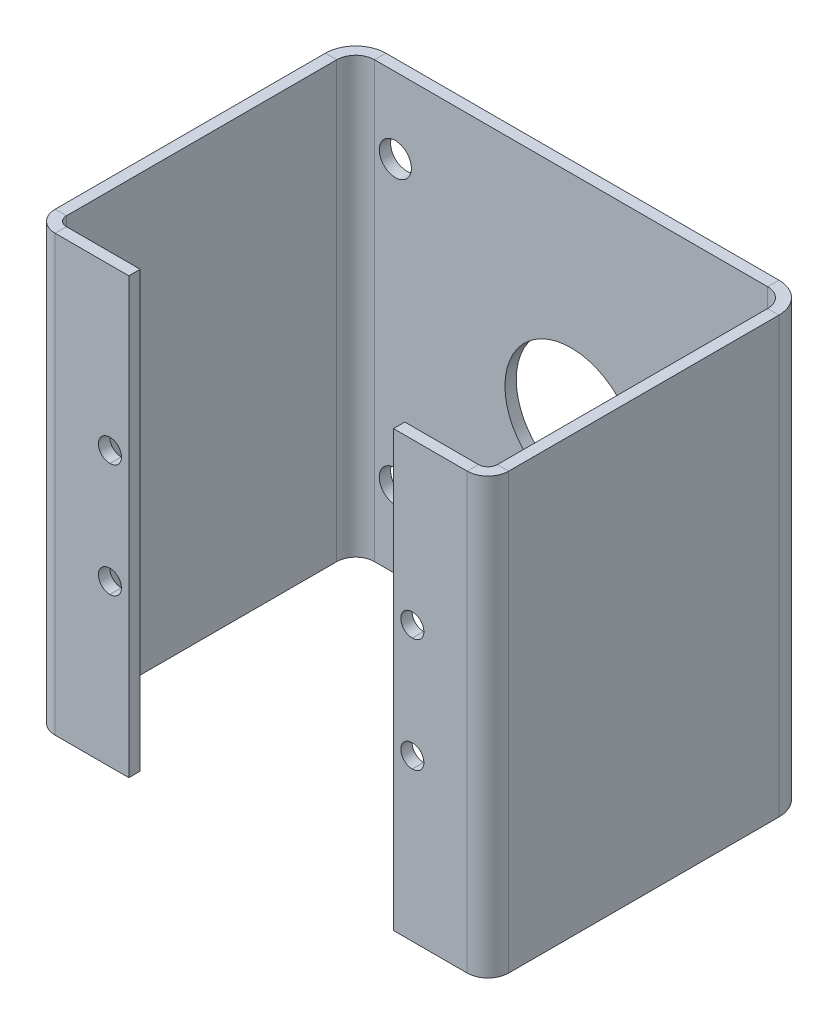
SolidWorks part; units mm, degrees
note: The reader was unsure of these and kept them because the rebuilt part matched: thickness of "Base-Flange1", "Edge-Flange1", "Edge-Flange2", "Sheet-Metal1", "Sheet-Metal2", "Sheet-Metal3", "Sheet-Metal4", "Sheet-Metal5", "Sheet-Metal7", "Sheet-Metal8", "Sheet-Metal9", "Sheet-Metal10"; flange length of "Edge-Flange1", "Edge-Flange2".
material "ASTM A36 Steel"
ref_plane "Front Plane" through (0, 0, 0) normal (0, 0, 1) x (1, 0, 0)
ref_plane "Top Plane" through (0, 0, 0) normal (0, 1, 0) x (1, 0, 0)
ref_plane "Right Plane" through (0, 0, 0) normal (1, 0, 0) x (0, 0, -1)
sketch "Sketch1" plane through (0, 0, 0) normal (0, 0, 1) x (1, 0, 0)
  line L1 (-60, -57.5) -> (60, -57.5)
  line L2 (-60, -57.5) -> (-60, 57.5)
  line L3 (-60, 57.5) -> (60, 57.5)
  line L4 (60, -57.5) -> (60, 57.5)
  line L5 (-60, -57.5) -> (60, 57.5) construction
  line L6 (-60, 57.5) -> (60, -57.5) construction
  point P0 (0, 0)
  dimension "D1" = 115
  dimension "D2" = 120
base flange "Base-Flange1" sketch "Sketch1" thickness 3 reverse thickness direction no parameters "D1"=2.5
edge flange "Edge-Flange1" sketch "Sketch10" flange profiles "Sketch10", "Sketch11" flange angle 90 flange length 85 flange position material inside bend radius 5 thickness 3 relief rectangular parameters "D6"=10, "D8"=1
sketch "Sketch10" plane through (60, 0, 0) normal (1, 0, 0) x (0, 1, 0)
  line L0 (-57.5, 0) -> (57.5, 0) construction
  line L1 (-57.5, 0) -> (57.5, 0)
  line L2 (-57.5, 0) -> (-57.5, 82)
  line L3 (-57.5, 82) -> (57.5, 82)
  line L4 (57.5, 82) -> (57.5, 0)
sketch "Sketch11" plane through (-60, 0, 0) normal (-1, 0, 0) x (0, -1, 0)
  line L0 (-57.5, 0) -> (57.5, 0) construction
  line L1 (-57.5, 0) -> (57.5, 0)
  line L2 (-57.5, 0) -> (-57.5, 82)
  line L3 (-57.5, 82) -> (57.5, 82)
  line L4 (57.5, 82) -> (57.5, 0)
bend "EdgeBend1" bend radius 5 bend angle 90 parameters "D5"=1
bend "EdgeBend2" bend radius 5 bend angle 90 parameters "D5"=2
edge flange "Edge-Flange2" sketch "Sketch16" flange profiles "Sketch16", "Sketch17" flange angle 90 flange length 25 flange position material inside bend radius 2.5 thickness 3 relief rectangular parameters "D6"=10, "D8"=1
sketch "Sketch16" plane through (-57, 0, 82) normal (0, 0, 1) x (0, -1, 0)
  line L2 (-57.5, 0) -> (-57.5, 22)
  line L3 (-57.5, 22) -> (57.5, 22)
  line L4 (57.5, 22) -> (57.5, 0)
  line L5 (57.5, 0) -> (-57.5, 0) construction
  line L6 (57.5, 0) -> (-57.5, 0)
sketch "Sketch17" plane through (57, 0, 82) normal (0, 0, 1) x (0, 1, 0)
  line L2 (-57.5, 0) -> (-57.5, 22)
  line L3 (-57.5, 22) -> (57.5, 22)
  line L4 (57.5, 22) -> (57.5, 0)
  line L5 (57.5, 0) -> (-57.5, 0) construction
  line L6 (57.5, 0) -> (-57.5, 0)
bend "EdgeBend3" bend radius 2.5 bend angle 90 parameters "D5"=3
bend "EdgeBend4" bend radius 2.5 bend angle 90 parameters "D5"=4
sketch "Sketch18" plane through (0, 0, 82) normal (0, 0, 1) x (1, 0, 0)
  line L0 (-40.05, -15) -> (-39.95, -15) construction
  line L1 (-40.05, -12) -> (-39.95, -12)
  line L2 (-40.05, -18) -> (-39.95, -18)
  line L4 (-54.5, -57.5) -> (-35, -57.5) construction
  line L5 (-60, -57.5) -> (-60, 57.5) construction
  arc A0 (-40.05, -12) -> (-40.05, -18) centre (-40.05, -15) ccw
  arc A1 (-39.95, -18) -> (-39.95, -12) centre (-39.95, -15) ccw
  point P2 (-40, -15)
  point P11 (-44.75, -57.5)
  dimension "D1" = 3
  dimension "D2" = 0.1
  dimension "D3" = 20
  dimension "D4" = 42.5
extrude "Cut-Extrude1" cut sketch "Sketch18" against normal blind 10 normal cut yes
pattern_linear "LPattern1" count 2 spacing 30 along (0, 1, 0) of "Cut-Extrude1"
pattern_linear "LPattern2" count 2 spacing 80 along (1, 0, 0) of "LPattern1", "Cut-Extrude1"
sketch "Sketch19" plane through (0, 0, -3) normal (0, 0, -1) x (-1, 0, 0)
  line L0 (-60, 57.5) -> (-60, -57.5) construction
  line L2 (52, -57.5) -> (-52, -57.5) construction
  circle A0 centre (-46.5, -37.5) radius 4.25
  circle A1 centre (46.5, -37.5) radius 4.25
  dimension "D1" = 13.5
  dimension "D2" = 8.5
  dimension "D3" = 93
  dimension "D4" = 20
extrude "Cut-Extrude2" cut sketch "Sketch19" against normal blind 10 normal cut yes
pattern_linear "LPattern3" count 2 spacing 75 along (0, 1, 0) of "Cut-Extrude2"
sketch "Sketch20" plane through (0, 0, -3) normal (0, 0, -1) x (-1, 0, 0)
  line L0 (60, -57.5) -> (-60, 57.5) construction
  circle A0 centre (0, 0) radius 17.5
  dimension "D1" = 35
extrude "Cut-Extrude3" cut sketch "Sketch20" against normal blind 10 normal cut yes
sketch "Bend-Lines1" [suppressed] plane through (0, 0, 0) normal (0, 1, 0) x (1, 0, 0)
sketch "Bounding-Box1" [suppressed] plane through (0, 0, 0) normal (0, 1, 0) x (1, 0, 0)
sheet metal parameters "Sheet-Metal1" thickness 3 parameters "D1"=2.5
flat pattern "Flat-Pattern1" [suppressed]
sketch "Bend-Lines2" plane through (0, 0, 0) normal (0, 1, 0) x (1, 0, 0)
sketch3d "Bounding-Box2" [suppressed]
  line L0 (-100, -42.5, 0) -> (100, -42.5, 0) construction
  line L1 (-100, 42.5, 0) -> (100, 42.5, 0) construction
  line L2 (-100, -42.5, 0) -> (-100, 42.5, 0) construction
  line L3 (100, -42.5, 0) -> (100, 42.5, 0) construction
sheet metal parameters "Sheet-Metal2" thickness 3 parameters "D1"=2.5, "D7"=5
flat pattern "Flat-Pattern1"
sketch "Bend-Lines2" plane through (0, 0, 0) normal (0, 0, 1) x (1, 0, 0)
  line L0 (-97.1051, 42.5) -> (-97.1051, -42.5) construction
  line L1 (97.1051, -42.5) -> (97.1051, 42.5) construction
  line L2 (-97.1051, 42.5) -> (-97.1051, -42.5) construction
  line L3 (97.1051, -42.5) -> (97.1051, 42.5) construction
sketch3d "Bounding-Box2" [suppressed]
  line L0 (-179.2102, -42.5, 0) -> (179.2102, -42.5, 0) construction
  line L1 (-179.2102, 42.5, 0) -> (179.2102, 42.5, 0) construction
  line L2 (-179.2102, -42.5, 0) -> (-179.2102, 42.5, 0) construction
  line L3 (179.2102, -42.5, 0) -> (179.2102, 42.5, 0) construction
bend of the flat pattern "Flatten-<EdgeBend1>1"
bend of the flat pattern "Flatten-<EdgeBend2>1"
sheet metal parameters "Sheet-Metal3" thickness 3 parameters "D1"=2.5, "D7"=5
flat pattern "Flat-Pattern1"
sketch "Bend-Lines2" plane through (0, 0, 0) normal (0, 0, 1) x (1, 0, 0)
  line L0 (-77.1051, 57.5) -> (-77.1051, -57.5) construction
  line L1 (77.1051, -57.5) -> (77.1051, 57.5) construction
  line L2 (-77.1051, 57.5) -> (-77.1051, -57.5) construction
  line L3 (77.1051, -57.5) -> (77.1051, 57.5) construction
  line L4 (156.8518, -57.5) -> (156.8518, 57.5) construction
  line L5 (-156.8518, 57.5) -> (-156.8518, -57.5) construction
  line L6 (156.8518, -57.5) -> (156.8518, 57.5) construction
  line L7 (-156.8518, 57.5) -> (-156.8518, -57.5) construction
sketch3d "Bounding-Box2" [suppressed]
  line L0 (-179.4934, -57.5, 0) -> (179.4934, -57.5, 0) construction
  line L1 (-179.4934, 57.5, 0) -> (179.4934, 57.5, 0) construction
  line L2 (-179.4934, -57.5, 0) -> (-179.4934, 57.5, 0) construction
  line L3 (179.4934, -57.5, 0) -> (179.4934, 57.5, 0) construction
bend of the flat pattern "Flatten-<EdgeBend1>1"
bend of the flat pattern "Flatten-<EdgeBend2>1"
bend of the flat pattern "Flatten-<EdgeBend3>1"
bend of the flat pattern "Flatten-<EdgeBend4>1"
sheet metal parameters "Sheet-Metal4" thickness 3 parameters "D1"=2.5, "D7"=5
flat pattern "Flat-Pattern1"
sketch "Bend-Lines2" plane through (0, 0, 0) normal (0, 0, 1) x (1, 0, 0)
  line L0 (-77.1051, 57.5) -> (-77.1051, -57.5) construction
  line L1 (77.1051, -57.5) -> (77.1051, 57.5) construction
  line L2 (-77.1051, 57.5) -> (-77.1051, -57.5) construction
  line L3 (77.1051, -57.5) -> (77.1051, 57.5) construction
  line L4 (156.8518, -57.5) -> (156.8518, 57.5) construction
  line L5 (-156.8518, 57.5) -> (-156.8518, -57.5) construction
  line L6 (156.8518, -57.5) -> (156.8518, 57.5) construction
  line L7 (-156.8518, 57.5) -> (-156.8518, -57.5) construction
sketch3d "Bounding-Box2" [suppressed]
  line L0 (-179.4934, -57.5, 0) -> (179.4934, -57.5, 0) construction
  line L1 (-179.4934, 57.5, 0) -> (179.4934, 57.5, 0) construction
  line L2 (-179.4934, -57.5, 0) -> (-179.4934, 57.5, 0) construction
  line L3 (179.4934, -57.5, 0) -> (179.4934, 57.5, 0) construction
bend of the flat pattern "Flatten-<EdgeBend1>1"
bend of the flat pattern "Flatten-<EdgeBend2>1"
bend of the flat pattern "Flatten-<EdgeBend3>1"
bend of the flat pattern "Flatten-<EdgeBend4>1"
sheet metal parameters "Sheet-Metal5" thickness 3 parameters "D1"=2.5, "D7"=5
flat pattern "Flat-Pattern1"
sketch "Bend-Lines2" plane through (0, 0, 0) normal (0, 0, 1) x (1, 0, 0)
  line L0 (-77.1051, 57.5) -> (-77.1051, -57.5) construction
  line L1 (77.1051, -57.5) -> (77.1051, 57.5) construction
  line L2 (-77.1051, 57.5) -> (-77.1051, -57.5) construction
  line L3 (77.1051, -57.5) -> (77.1051, 57.5) construction
  line L4 (156.8518, -57.5) -> (156.8518, 57.5) construction
  line L5 (-156.8518, 57.5) -> (-156.8518, -57.5) construction
  line L6 (156.8518, -57.5) -> (156.8518, 57.5) construction
  line L7 (-156.8518, 57.5) -> (-156.8518, -57.5) construction
sketch3d "Bounding-Box2" [suppressed]
  line L0 (-179.4934, -57.5, 0) -> (179.4934, -57.5, 0) construction
  line L1 (-179.4934, 57.5, 0) -> (179.4934, 57.5, 0) construction
  line L2 (-179.4934, -57.5, 0) -> (-179.4934, 57.5, 0) construction
  line L3 (179.4934, -57.5, 0) -> (179.4934, 57.5, 0) construction
bend of the flat pattern "Flatten-<EdgeBend1>1"
bend of the flat pattern "Flatten-<EdgeBend2>1"
bend of the flat pattern "Flatten-<EdgeBend3>1"
bend of the flat pattern "Flatten-<EdgeBend4>1"
sheet metal parameters "Sheet-Metal7" thickness 3 parameters "D1"=2.5, "D7"=5
flat pattern "Flat-Pattern1"
sketch "Bend-Lines2" plane through (0, 0, 0) normal (0, 0, 1) x (1, 0, 0)
  line L0 (-77.1051, 57.5) -> (-77.1051, -57.5) construction
  line L1 (77.1051, -57.5) -> (77.1051, 57.5) construction
  line L2 (-77.1051, 57.5) -> (-77.1051, -57.5) construction
  line L3 (77.1051, -57.5) -> (77.1051, 57.5) construction
  line L4 (156.8518, -57.5) -> (156.8518, 57.5) construction
  line L5 (-156.8518, 57.5) -> (-156.8518, -57.5) construction
  line L6 (156.8518, -57.5) -> (156.8518, 57.5) construction
  line L7 (-156.8518, 57.5) -> (-156.8518, -57.5) construction
sketch3d "Bounding-Box2" [suppressed]
  line L0 (-179.4934, -57.5, 0) -> (179.4934, -57.5, 0) construction
  line L1 (-179.4934, 57.5, 0) -> (179.4934, 57.5, 0) construction
  line L2 (-179.4934, -57.5, 0) -> (-179.4934, 57.5, 0) construction
  line L3 (179.4934, -57.5, 0) -> (179.4934, 57.5, 0) construction
bend of the flat pattern "Flatten-<EdgeBend1>1"
bend of the flat pattern "Flatten-<EdgeBend2>1"
bend of the flat pattern "Flatten-<EdgeBend3>1"
bend of the flat pattern "Flatten-<EdgeBend4>1"
sheet metal parameters "Sheet-Metal8" thickness 3 parameters "D1"=2.5, "D7"=5
flat pattern "Flat-Pattern1"
sketch "Bend-Lines2" plane through (0, 0, 0) normal (0, 0, 1) x (1, 0, 0)
  line L0 (-77.1051, 57.5) -> (-77.1051, -57.5) construction
  line L1 (77.1051, -57.5) -> (77.1051, 57.5) construction
  line L2 (-77.1051, 57.5) -> (-77.1051, -57.5) construction
  line L3 (77.1051, -57.5) -> (77.1051, 57.5) construction
  line L4 (156.8518, -57.5) -> (156.8518, 57.5) construction
  line L5 (-156.8518, 57.5) -> (-156.8518, -57.5) construction
  line L6 (156.8518, -57.5) -> (156.8518, 57.5) construction
  line L7 (-156.8518, 57.5) -> (-156.8518, -57.5) construction
sketch3d "Bounding-Box2" [suppressed]
  line L0 (-179.4934, -57.5, 0) -> (179.4934, -57.5, 0) construction
  line L1 (-179.4934, 57.5, 0) -> (179.4934, 57.5, 0) construction
  line L2 (-179.4934, -57.5, 0) -> (-179.4934, 57.5, 0) construction
  line L3 (179.4934, -57.5, 0) -> (179.4934, 57.5, 0) construction
bend of the flat pattern "Flatten-<EdgeBend1>1"
bend of the flat pattern "Flatten-<EdgeBend2>1"
bend of the flat pattern "Flatten-<EdgeBend3>1"
bend of the flat pattern "Flatten-<EdgeBend4>1"
sheet metal parameters "Sheet-Metal9" thickness 3 parameters "D1"=2.5, "D7"=5
flat pattern "Flat-Pattern1"
sketch "Bend-Lines2" plane through (0, 0, 0) normal (0, 0, 1) x (1, 0, 0)
  line L0 (-77.1051, 57.5) -> (-77.1051, -57.5) construction
  line L1 (77.1051, -57.5) -> (77.1051, 57.5) construction
  line L2 (-77.1051, 57.5) -> (-77.1051, -57.5) construction
  line L3 (77.1051, -57.5) -> (77.1051, 57.5) construction
  line L4 (156.8518, -57.5) -> (156.8518, 57.5) construction
  line L5 (-156.8518, 57.5) -> (-156.8518, -57.5) construction
  line L6 (156.8518, -57.5) -> (156.8518, 57.5) construction
  line L7 (-156.8518, 57.5) -> (-156.8518, -57.5) construction
sketch3d "Bounding-Box2" [suppressed]
  line L0 (-179.4934, -57.5, 0) -> (179.4934, -57.5, 0) construction
  line L1 (-179.4934, 57.5, 0) -> (179.4934, 57.5, 0) construction
  line L2 (-179.4934, -57.5, 0) -> (-179.4934, 57.5, 0) construction
  line L3 (179.4934, -57.5, 0) -> (179.4934, 57.5, 0) construction
bend of the flat pattern "Flatten-<EdgeBend1>1"
bend of the flat pattern "Flatten-<EdgeBend2>1"
bend of the flat pattern "Flatten-<EdgeBend3>1"
bend of the flat pattern "Flatten-<EdgeBend4>1"
sheet metal parameters "Sheet-Metal10" thickness 3 parameters "D1"=2.5, "D7"=5
flat pattern "Flat-Pattern1"
sketch "Bend-Lines2" plane through (0, 0, 0) normal (0, 0, 1) x (1, 0, 0)
  line L0 (-57.1051, 57.5) -> (-57.1051, -57.5) construction
  line L1 (57.1051, -57.5) -> (57.1051, 57.5) construction
  line L2 (-57.1051, 57.5) -> (-57.1051, -57.5) construction
  line L3 (57.1051, -57.5) -> (57.1051, 57.5) construction
  line L4 (136.8518, -57.5) -> (136.8518, 57.5) construction
  line L5 (-136.8518, 57.5) -> (-136.8518, -57.5) construction
  line L6 (136.8518, -57.5) -> (136.8518, 57.5) construction
  line L7 (-136.8518, 57.5) -> (-136.8518, -57.5) construction
sketch3d "Bounding-Box2" [suppressed]
  line L0 (-159.4934, -57.5, 0) -> (159.4934, -57.5, 0) construction
  line L1 (-159.4934, 57.5, 0) -> (159.4934, 57.5, 0) construction
  line L2 (-159.4934, -57.5, 0) -> (-159.4934, 57.5, 0) construction
  line L3 (159.4934, -57.5, 0) -> (159.4934, 57.5, 0) construction
bend of the flat pattern "Flatten-<EdgeBend1>1"
bend of the flat pattern "Flatten-<EdgeBend2>1"
bend of the flat pattern "Flatten-<EdgeBend3>1"
bend of the flat pattern "Flatten-<EdgeBend4>1"
